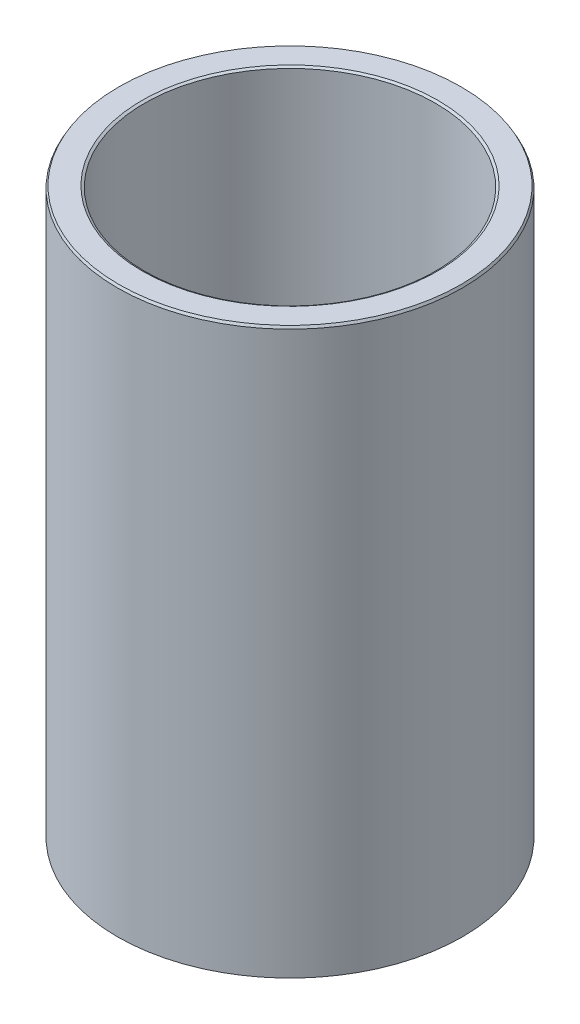
SolidWorks part; units mm, degrees
ref_plane "Front Plane" through (0, 0, 0) normal (0, 0, 1) x (1, 0, 0)
ref_plane "Top Plane" through (0, 0, 0) normal (0, 1, 0) x (1, 0, 0)
ref_plane "Right Plane" through (0, 0, 0) normal (1, 0, 0) x (0, 0, -1)
sketch "Sketch1" plane through (0, 0, 0) normal (0, 1, 0) x (1, 0, 0)
  circle A0 centre (0, 0) radius 52.5
  dimension "SLEEVE_OD" = 105
extrude "Boss-Extrude1" add sketch "Sketch1" along normal blind 172.153
sketch "Sketch2" plane through (0, 0, 0) normal (0, 1, 0) x (1, 0, 0)
  circle A0 centre (0, 0) radius 44.2775
  dimension "BORE_D" = 88.555
extrude "Cut-Extrude1" cut sketch "Sketch2" along normal through all
chamfer "Chamfer1" distance 0.7166 angle 30 4 edges at (0, 172.153, 44.2775) (0, 0, 44.2775) (0, 0, 52.5) (0, 172.153, 52.5) first distance on face at (0, 172.153, 44.2775) first distance on face at (0, 0, 44.2775) first distance on face at (0, 172.153, 52.5)
